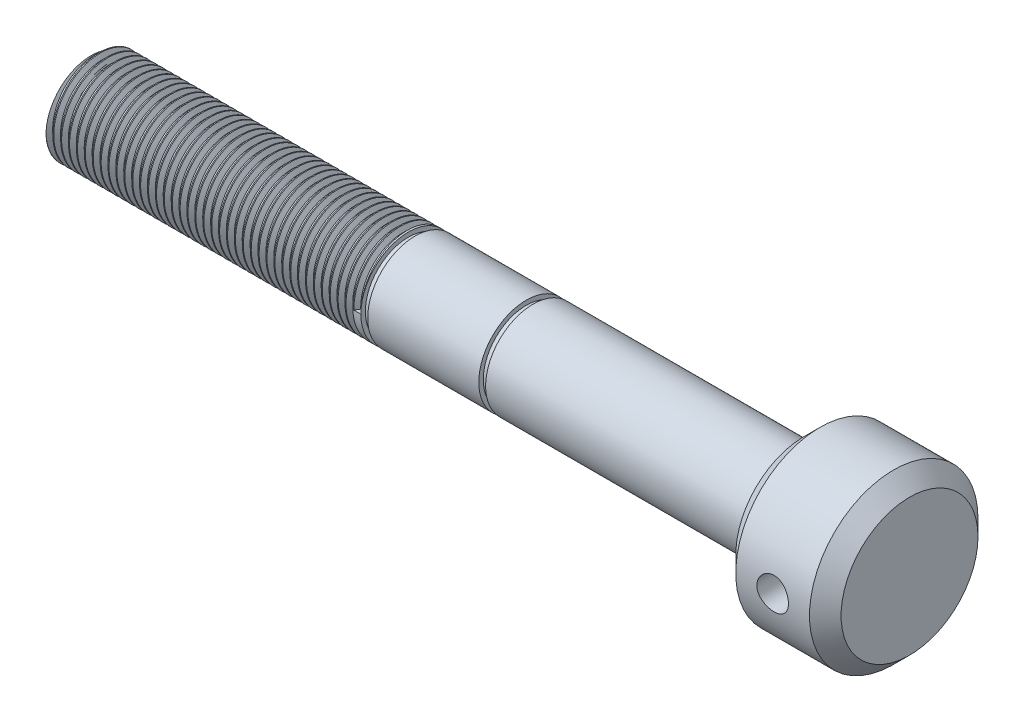
SolidWorks part; units mm, degrees
ref_plane "Piano frontale" through (0, 0, 0) normal (0, 0, 1) x (1, 0, 0)
ref_plane "Piano superiore" through (0, 0, 0) normal (0, 1, 0) x (1, 0, 0)
ref_plane "Piano destro" through (0, 0, 0) normal (1, 0, 0) x (0, 0, -1)
sketch "Schizzo1" plane through (0, 0, 0) normal (1, 0, 0) x (0, 0, -1)
  circle A0 centre (0, 0) radius 16
  dimension "D1" = 32
extrude "Estrusione-Estrusione1" add sketch "Schizzo1" along normal blind 20
sketch "Schizzo2" plane through (0, 0, 0) normal (0, 0, 1) x (1, 0, 0)
  line L1 (0, 16) -> (0, -16) construction
  circle A0 centre (10, 0) radius 3
  dimension "D2" = 6
  dimension "D1" = 10
extrude "Taglio-Estrusione1" cut sketch "Schizzo2" against normal through all both and the other way through all
sketch "Schizzo3" plane through (0, 0, 0) normal (1, 0, 0) x (0, 0, -1)
  circle A0 centre (0, 0) radius 9
  dimension "D1" = 18
extrude "Estrusione-Estrusione2" add sketch "Schizzo3" against normal blind 135
cosmetic thread "Filettatura cosmetica2" parameters "D2"=16.344
cosmetic thread "Filettatura cosmetica3" parameters "D2"=16.344
sketch "Schizzo4" plane through (0, 0, 0) normal (0, 0, 1) x (1, 0, 0)
  line L0 (0, 0) -> (-146.9482, 0) construction
  line L1 (0, 9) -> (-135, 9) construction
  line L2 (-52.8, 9) -> (-51.5, 9)
  line L3 (-52.8, 9) -> (-52.8, 8.15)
  line L4 (-52.8, 8.15) -> (-51.5, 8.15)
  line L5 (-51.5, 9) -> (-51.5, 8.15)
  line L6 (20, -16) -> (20, 16) construction
  line L9 (-75.2, 9) -> (-73.9, 9)
  line L10 (-75.2, 9) -> (-75.2, 8.15)
  line L11 (-75.2, 8.15) -> (-73.9, 8.15)
  line L12 (-73.9, 9) -> (-73.9, 8.15)
  dimension "D1" = 8.15
  dimension "D2" = 71.5
  dimension "D3" = 1.3
  dimension "D4" = 1.3
  dimension "D5" = 22.4
revolve "Taglia-Rivoluzione1" cut sketch "Schizzo4" angle 360 about L0
chamfer "Smusso1" distance 3 angle 45 2 edges at (0, 0, -16) (20, 0, -16)
thread "Filettatura1" pitch 1.5 method cut profile "Profilo filettatura1" start angle 0, offset 0, length 0, pitch 1.5, diameter 18
ref_plane "Piano1" through (-75.2, 0, 9) normal (0, -1, 0) x (0, 0, 1)
sketch "Profilo filettatura1" plane through (-75.2, 0, 9) normal (0, -1, 0) x (0, 0, 1)
  line L0 (0, 0) -> (0, 1.5) construction
  line L11 (0, 0) -> (0, 1.3125)
  line L12 (0, 1.3125) -> (-0.8119, 0.8437)
  line L13 (-0.8119, 0.8437) -> (-0.8119, 0.4687)
  line L15 (-0.8119, 0.4687) -> (0, 0)
  line L17 (-0.8119, 0.6562) -> (0, 0.6562) construction
  point P2 (0, 0)
  dimension "Pitch" = 1.5
  dimension "Profile_Angle" = 60
  dimension "Profile_Land" = 0.375
  dimension "Profile_Height" = 0.8119
